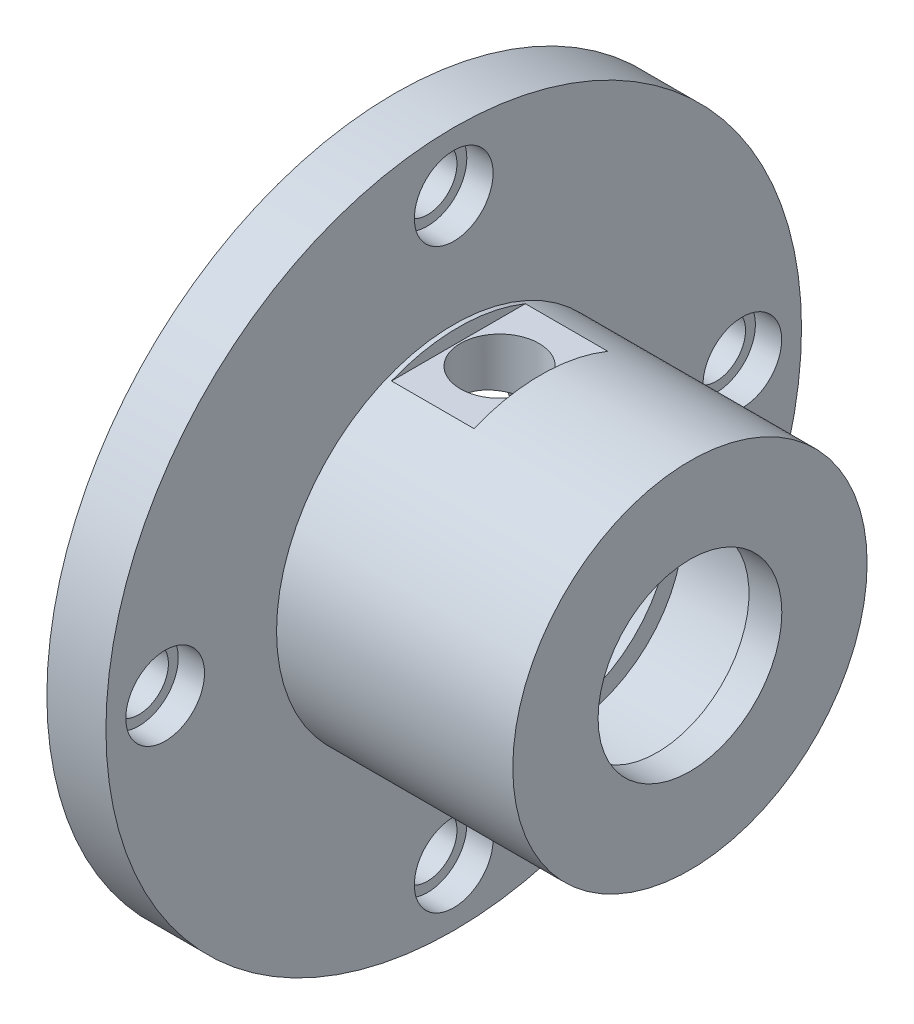
SolidWorks part; units mm, degrees
ref_plane "Front Plane" through (0, 0, 0) normal (0, 0, 1) x (1, 0, 0)
ref_plane "Top Plane" through (0, 0, 0) normal (0, 1, 0) x (1, 0, 0)
ref_plane "Right Plane" through (0, 0, 0) normal (1, 0, 0) x (0, 0, -1)
sketch "Sketch1" plane through (0, 0, 0) normal (1, 0, 0) x (0, 0, -1)
  circle A0 centre (0, 0) radius 26.5
  circle A2 centre (0, -21.9877) radius 2.25
  circle A3 centre (-21.9877, 0) radius 2.25
  circle A4 centre (0, 21.9877) radius 2.25
  circle A5 centre (21.9877, 0) radius 2.25
  point P14 (0, 0)
  dimension "D1" = 53
  dimension "D2" = 4
  dimension "D3" = 4.5
extrude "Boss-Extrude1" add sketch "Sketch1" along normal mid plane 22.5
sketch "Sketch2" plane through (11.25, 0, 0) normal (1, 0, 0) x (0, 0, -1)
  circle A0 centre (0, 0) radius 13.5
  circle A1 centre (0, 0) radius 26.5
  circle A2 centre (0, 0) radius 0.5
  circle M3 centre (0, 21.9877) radius 2.25
  circle M4 centre (0, -21.9877) radius 2.25
  circle M5 centre (0, 0) radius 26.5
  circle M6 centre (-21.9877, 0) radius 2.25
  circle M7 centre (21.9877, 0) radius 2.25
  dimension "D1" = 13
  dimension "D2" = 13
extrude "Cut-Extrude1" cut sketch "Sketch2" against normal blind 18 contours A0 M5 M4 M6 M7 M3 region at (11.25, 0, 25.7505)
sketch "Sketch3" plane through (-11.25, 0, 0) normal (-1, 0, 0) x (0, 0, 1)
  circle A0 centre (0, 0) radius 9
  dimension "D1" = 18
extrude "Cut-Extrude2" cut sketch "Sketch3" against normal blind 20
sketch "Sketch4" plane through (8.75, 0, 0) normal (-1, 0, 0) x (0, 0, 1)
  circle A0 centre (0, 0) radius 7
extrude "Cut-Extrude3" cut sketch "Sketch4" against normal blind 20
ref_plane "Plane1" through (1.25, 0, 0) normal (-1, 0, 0) x (0, 0, 1)
sketch "Sketch5" plane through (1.25, 0, 0) normal (-1, 0, 0) x (0, 0, 1)
  circle A0 centre (0, 0) radius 11
extrude "Cut-Extrude4" cut sketch "Sketch5" against normal mid plane 1
ref_axis "Axis1" through (26.9883, 0, 0) along (-1, 0, 0)
sketch "Sketch6" plane through (0, 0, 0) normal (0, 1, 0) x (1, 0, 0)
  line L0 (26.9883, 0) -> (-32.12, 0) construction
  line L1 (11.25, -13.5) -> (11.25, 13.5) construction
  circle A0 centre (-3.25, 0) radius 3
  dimension "D1" = 14.5
extrude "Cut-Extrude5" cut sketch "Sketch6" along normal blind 33
ref_plane "Plane3" through (0, 13.5, 0) normal (0, 1, 0) x (1, 0, 0)
sketch "Sketch8" plane through (0, 13.5, 0) normal (0, 1, 0) x (1, 0, 0)
  line L1 (-0.1089, -6) -> (-6.3911, -6)
  line L2 (-0.1089, -6) -> (-0.1089, 6)
  line L3 (-0.1089, 6) -> (-6.3911, 6)
  line L4 (-6.3911, -6) -> (-6.3911, 6)
  line L5 (-0.1089, -6) -> (-6.3911, 6) construction
  line L6 (-0.1089, 6) -> (-6.3911, -6) construction
  point P0 (-3.25, 0)
  dimension "D1" = 12
extrude "Cut-Extrude6" cut sketch "Sketch8" against normal blind 1
sketch "Sketch9" plane through (-6.75, 0, 0) normal (1, 0, 0) x (0, 0, -1)
  circle A0 centre (0, 21.9877) radius 3
  circle A1 centre (21.9877, 0) radius 3
  circle A2 centre (0, -21.9877) radius 3
  circle A3 centre (-21.9877, 0) radius 3
  point P12 (0, 0)
  dimension "D1" = 4
extrude "Cut-Extrude7" cut sketch "Sketch9" against normal blind 2
